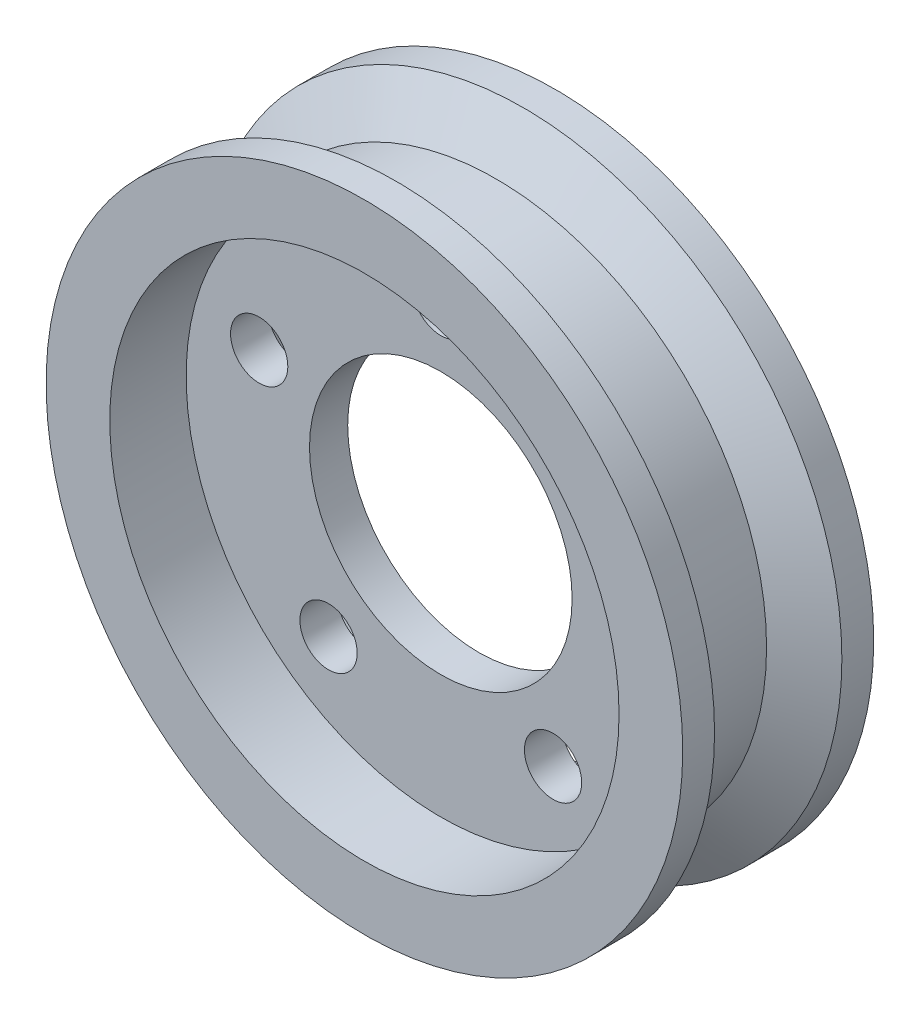
SolidWorks part; units mm, degrees
ref_plane "Front Plane" through (0, 0, 0) normal (0, 0, 1) x (1, 0, 0)
ref_plane "Top Plane" through (0, 0, 0) normal (0, 1, 0) x (1, 0, 0)
ref_plane "Right Plane" through (0, 0, 0) normal (1, 0, 0) x (0, 0, -1)
sketch "Sketch1" plane through (0, 0, 0) normal (0, 0, 1) x (1, 0, 0)
  line L0 (-1.5216, 1.9836) -> (-1.5216, -2.0164)
  line L1 (1.4783, 2.0161) -> (1.4783, -1.9839)
  circle A0 centre (0, 0) radius 10
  arc A2 (-1.5216, 1.9836) -> (1.4783, 2.0161) centre (0, 0) cw
  arc A3 (-1.5216, -2.0164) -> (1.4783, -1.9839) centre (-0.0433, -0.0002) ccw
extrude "Boss-Extrude1" add sketch "Sketch1" along normal mid plane 6
sketch "Sketch2" plane through (0, 0, 3) normal (0, 0, 1) x (1, 0, 0)
  circle A0 centre (0, 0) radius 8
  dimension "D1" = 16
extrude "Cut-Extrude1" cut sketch "Sketch2" against normal blind 2.4
sketch "Sketch3" plane through (0, 0, 0.6) normal (0, 0, 1) x (1, 0, 0)
  circle A0 centre (0, 6) radius 0.9
  circle A1 centre (5.7063, 1.8541) radius 0.9
  circle A2 centre (3.5267, -4.8541) radius 0.9
  circle A3 centre (-3.5267, -4.8541) radius 0.9
  circle A4 centre (-5.7063, 1.8541) radius 0.9
  point P13 (0, 0)
  dimension "D1" = 6
  dimension "D2" = 1.8
  dimension "D3" = 5
ref_plane "Plane1" through (-1.5216, -2.0164, 0.6) normal (0.8065, -0.5913, 0) x (0, 0, -1)
mirror "Mirror1" about plane through (0, 0, 0) normal (0, 0, 1) of "Cut-Extrude1"
sketch "Sketch5" plane through (0, 0, 0) normal (0, 1, 0) x (1, 0, 0)
  line L0 (0, 0) -> (0, 5.2467) construction
  line L1 (-10, 2) -> (-8.5, 1.134)
  line L2 (-10, 3) -> (-10, -3) construction
  line L3 (-8.5, 1.134) -> (-8.5, -1.134)
  line L4 (-8.5, -1.134) -> (-10, -2)
  line L5 (-10, -2) -> (-10, 2)
  point P10 (-10, 0)
  dimension "D1" = 1
  dimension "D2" = 1
  dimension "D3" = 60
  dimension "D4" = 60
  dimension "D5" = 1.5
revolve "Cut-Revolve1" cut sketch "Sketch5" angle 360 about L0
sketch "Sketch6" plane through (0, 0, -0.6) normal (0, 0, -1) x (-1, 0, 0)
  circle A0 centre (0, 0) radius 4.125
  dimension "D1" = 8.25
extrude "Cut-Extrude2" cut sketch "Sketch6" against normal through all
extrude "Cut-Extrude3" cut sketch "Sketch3" against normal through all contours A3 | A0 | A1 | A2 | A4 region at (-3.5267, -4.8541, 0.6)
